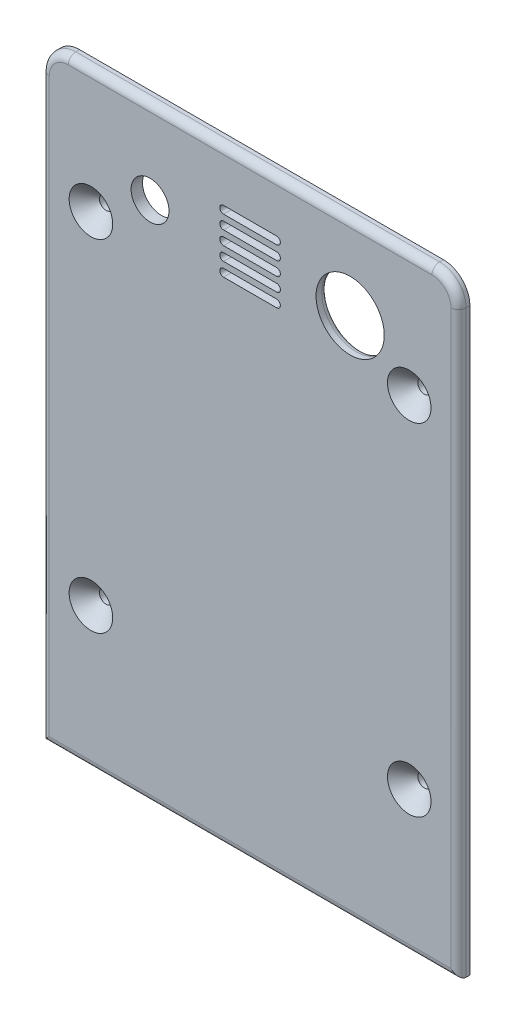
SolidWorks part; units mm, degrees
ref_plane "Front Plane" through (0, 0, 0) normal (0, 0, 1) x (1, 0, 0)
ref_plane "Top Plane" through (0, 0, 0) normal (0, 1, 0) x (1, 0, 0)
ref_plane "Right Plane" through (0, 0, 0) normal (1, 0, 0) x (0, 0, -1)
sketch "Sketch1" plane through (0, 0, 0) normal (0, 0, 1) x (1, 0, 0)
  line L1 (0, 0) -> (110, 0)
  line L2 (0, 0) -> (0, 153)
  line L3 (7, 160) -> (103, 160)
  line L4 (110, 0) -> (110, 153)
  arc A0 (103, 160) -> (110, 153) centre (103, 153) cw
  arc A1 (0, 153) -> (7, 160) centre (7, 153) cw
  point P7 (110, 160)
  point P10 (0, 160)
  dimension "D3" = 7
  dimension "D1" = 110
  dimension "D2" = 160
extrude "Boss-Extrude1" add sketch "Sketch1" along normal blind 3
fillet "Fillet1" radius 2 6 edges at (2.0503, 157.9497, 3) (55, 160, 3) (107.9497, 157.9497, 3) (110, 76.5, 3) (55, 0, 3) (0, 76.5, 3)
sketch "Sketch3" plane through (0, 0, 0) normal (0, 0, -1) x (-1, 0, 0)
  line L0 (0, 0) -> (-110, 0) construction
  line L1 (-103, 0) -> (-7, 0)
  line L2 (-103, 0) -> (-103, 152.5)
  line L3 (-103, 152.5) -> (-7, 152.5)
  line L4 (-7, 0) -> (-7, 152.5)
  line L5 (-101.4, 1.6) -> (-101.4, 33.5)
  line L6 (-101.4, 150.9) -> (-8.6, 150.9)
  line L7 (-8.6, 1.6) -> (-8.6, 33.5)
  line L8 (-101.4, 1.6) -> (-8.6, 1.6)
  line L9 (-97, 131.5) -> (-101.4, 131.5)
  line L10 (-97, 123.5) -> (-101.4, 123.5)
  line L11 (-13, 131.5) -> (-8.6, 131.5)
  line L12 (-8.6, 123.5) -> (-13, 123.5)
  line L13 (-13, 33.5) -> (-8.6, 33.5)
  line L14 (-13, 41.5) -> (-8.6, 41.5)
  line L15 (-97, 41.5) -> (-101.4, 41.5)
  line L16 (-101.4, 33.5) -> (-97, 33.5)
  line L17 (-101.4, 41.5) -> (-101.4, 123.5)
  line L18 (-8.6, 41.5) -> (-8.6, 123.5)
  line L19 (-101.4, 1.6) -> (-101.4, 150.9) construction
  line L20 (-8.6, 131.5) -> (-8.6, 150.9)
  line L21 (-8.6, 1.6) -> (-8.6, 150.9) construction
  line L22 (-101.4, 131.5) -> (-101.4, 150.9)
  arc A0 (-97, 123.5) -> (-97, 131.5) centre (-97, 127.5) ccw
  arc A1 (-13, 131.5) -> (-13, 123.5) centre (-13, 127.5) ccw
  arc A2 (-97, 33.5) -> (-97, 41.5) centre (-97, 37.5) ccw
  arc A3 (-13, 41.5) -> (-13, 33.5) centre (-13, 37.5) ccw
  point P6 (-55, 0)
  point P7 (-55, 0)
  dimension "D4" = 8
  dimension "D5" = 6
  dimension "D6" = 6
  dimension "D8" = 90
  dimension "D1" = 96
  dimension "D2" = 152.5
  dimension "D7" = 25
  dimension "D3" = 1.6
extrude "Boss-Extrude2" add sketch "Sketch3" along normal blind 3.9
sketch "Sketch4" plane through (0, 0, -3.9) normal (0, 0, -1) x (-1, 0, 0)
  circle A0 centre (-97, 127.5) radius 1.75
  circle A1 centre (-13, 127.5) radius 1.75
  circle A2 centre (-13, 37.5) radius 1.75
  circle A3 centre (-97, 37.5) radius 1.75
  dimension "D1" = 3.5
extrude "Cut-Extrude1" cut sketch "Sketch4" against normal up to next
chamfer "Chamfer1" distance 4 angle 45 4 edges at (95.25, 37.5, 3) (11.25, 37.5, 3) (11.25, 127.5, 3) (95.25, 127.5, 3)
sketch "Sketch5" plane through (0, 0, 0) normal (0, 0, -1) x (-1, 0, 0)
  line L0 (-8.6, 150.9) -> (-101.4, 150.9) construction
  line L1 (-8.6, 131.5) -> (-8.6, 150.9) construction
  line L2 (-101.4, 150.9) -> (-101.4, 131.5) construction
  circle A0 centre (-28.6, 137.9) radius 5
  circle A1 centre (-81.4, 137.9) radius 9
  dimension "D1" = 13
  dimension "D2" = 20
  dimension "D3" = 10
  dimension "D4" = 18
  dimension "D5" = 20
extrude "Cut-Extrude2" cut sketch "Sketch5" against normal through all
fillet "Fillet2" radius 1.5 1 edges at (72.4, 137.9, 0)
sketch "Sketch7" plane through (0, 0, 0) normal (0, 0, -1) x (-1, 0, 0)
  line L0 (-8.6, 150.9) -> (-101.4, 150.9) construction
  line L1 (-65, 147.9) -> (-45, 147.9)
  line L2 (-65, 147.9) -> (-65, 127.9)
  line L3 (-65, 127.9) -> (-45, 127.9)
  line L4 (-45, 147.9) -> (-45, 127.9)
  line L5 (-64, 146.9) -> (-46, 146.9)
  line L6 (-46, 146.9) -> (-46, 128.9)
  line L7 (-64, 128.9) -> (-46, 128.9)
  line L8 (-64, 146.9) -> (-64, 128.9)
  point P6 (-55, 150.9)
  point P7 (-55, 147.9)
  dimension "D1" = 20
  dimension "D2" = 20
  dimension "D3" = 3
  dimension "D4" = 1
extrude "Boss-Extrude3" add sketch "Sketch7" along normal up to surface (3.9 mm away) up to face at (95.25, 37.5, -3.9)
sketch "Sketch8" plane through (0, 0, 0) normal (0, 0, -1) x (-1, 0, 0)
  line L0 (-62, 145.4) -> (-48, 145.4) construction
  line L1 (-62, 146.4) -> (-48, 146.4)
  line L2 (-62, 144.4) -> (-48, 144.4)
  line L3 (-46, 146.9) -> (-64, 146.9) construction
  line L4 (-62, 141.8) -> (-48, 141.8) construction
  line L5 (-62, 142.8) -> (-48, 142.8)
  line L6 (-62, 140.8) -> (-48, 140.8)
  line L7 (-62, 138.2) -> (-48, 138.2) construction
  line L8 (-62, 139.2) -> (-48, 139.2)
  line L9 (-62, 137.2) -> (-48, 137.2)
  line L10 (-62, 134.6) -> (-48, 134.6) construction
  line L11 (-62, 135.6) -> (-48, 135.6)
  line L12 (-62, 133.6) -> (-48, 133.6)
  line L13 (-62, 131) -> (-48, 131) construction
  line L14 (-62, 132) -> (-48, 132)
  line L15 (-62, 130) -> (-48, 130)
  arc A0 (-62, 146.4) -> (-62, 144.4) centre (-62, 145.4) ccw
  arc A1 (-48, 144.4) -> (-48, 146.4) centre (-48, 145.4) ccw
  arc A2 (-62, 142.8) -> (-62, 140.8) centre (-62, 141.8) ccw
  arc A3 (-48, 140.8) -> (-48, 142.8) centre (-48, 141.8) ccw
  arc A4 (-62, 139.2) -> (-62, 137.2) centre (-62, 138.2) ccw
  arc A5 (-48, 137.2) -> (-48, 139.2) centre (-48, 138.2) ccw
  arc A6 (-62, 135.6) -> (-62, 133.6) centre (-62, 134.6) ccw
  arc A7 (-48, 133.6) -> (-48, 135.6) centre (-48, 134.6) ccw
  arc A8 (-62, 132) -> (-62, 130) centre (-62, 131) ccw
  arc A9 (-48, 130) -> (-48, 132) centre (-48, 131) ccw
  point P2 (-55, 145.4)
  point P9 (-55, 146.9)
  point P14 (-55, 141.8)
  point P21 (-55, 138.2)
  point P28 (-55, 134.6)
  point P35 (-55, 131)
  dimension "D2" = 1
  dimension "D1" = 14
  dimension "D3" = 1.5
  dimension "D4" = 5
extrude "Cut-Extrude3" cut sketch "Sketch8" against normal through all
